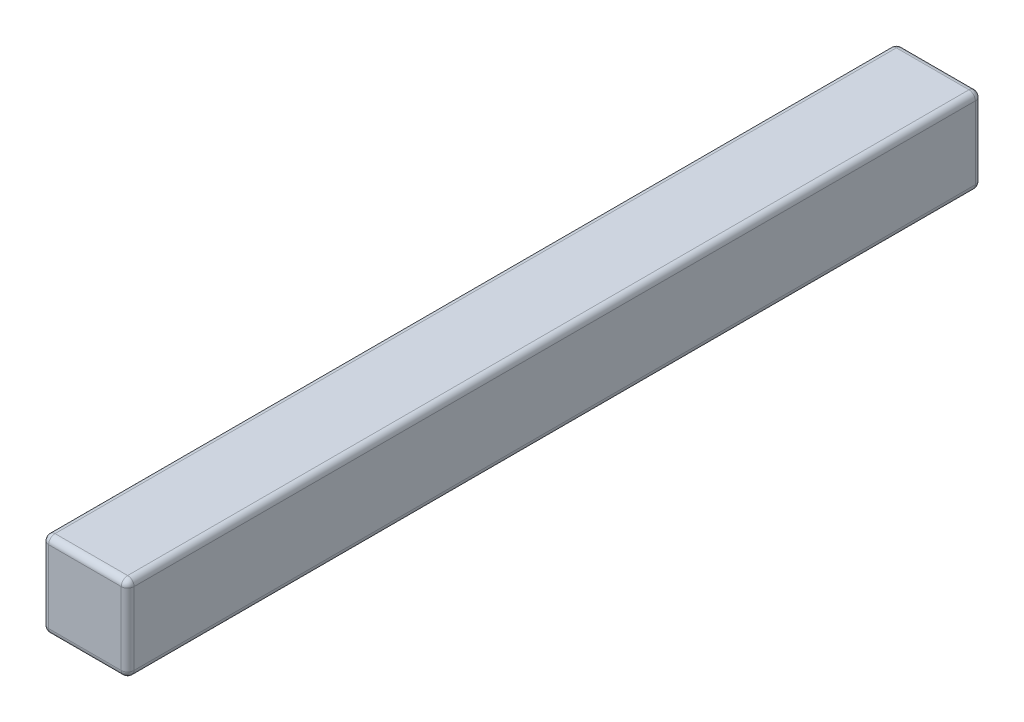
SolidWorks part; units mm, degrees
ref_plane "Front Plane" through (0, 0, 0) normal (0, 0, 1) x (1, 0, 0)
ref_plane "Top Plane" through (0, 0, 0) normal (0, 1, 0) x (1, 0, 0)
ref_plane "Right Plane" through (0, 0, 0) normal (1, 0, 0) x (0, 0, -1)
sketch "Sketch1" plane through (0, 0, 0) normal (0, 0, 1) x (1, 0, 0)
  line L3 (1, -1) -> (-1, -1)
  line L4 (1, -1) -> (1, 1)
  line L5 (1, 1) -> (-1, 1)
  line L6 (-1, -1) -> (-1, 1)
  line L7 (1, -1) -> (-1, 1) construction
  line L8 (1, 1) -> (-1, -1) construction
  point P0 (0, 0)
  dimension "Width" = 2
  dimension "Height" = 2
sketch "Sketch2" plane through (0, 0, 0) normal (1, 0, 0) x (0, 0, -1)
  line L2 (10, -1) -> (-10, -1)
  line L3 (10, -1) -> (10, 1)
  line L4 (10, 1) -> (-10, 1)
  line L5 (-10, -1) -> (-10, 1)
  line L6 (10, -1) -> (-10, 1) construction
  line L7 (10, 1) -> (-10, -1) construction
  point P0 (0, 0)
  point P4 (0, 0)
  point P15 (-7.8, 1)
  point P17 (7.8, 1)
  dimension "Length" = 20
  dimension "D1" = 2.2
  dimension "D2" = 2.2
sketch "Sketch3" plane through (0, 0, 0) normal (0, 0, 1) x (1, 0, 0)
  line L0 (1, -1) -> (1, 1) construction
  line L5 (1, -1) -> (-1, -1) construction
  line L6 (-1, -1) -> (-1, 1) construction
  line L7 (1, 1) -> (-1, 1) construction
  line L8 (1, -1) -> (1, 1)
  line L9 (1, -1) -> (-1, -1)
  line L10 (-1, -1) -> (-1, 1)
  line L11 (1, 1) -> (-1, 1)
extrude "Boss-Extrude1" add sketch "Sketch3" along normal up to vertex (10 mm away) and the other way up to vertex (10 mm away) up to point (0, 1, 10) other way up to point (0, 1, -10)
fillet "Fillet2" radius 0.15 12 edges at (-1, 0, -10) (0, -1, -10) (-1, 1, 0) (0, 1, -10) (1, 1, 0) (1, 0, -10) (1, -1, 0) (-1, 0, 10) (0, 1, 10) (1, 0, 10) (0, -1, 10) (-1, -1, 0)
ref_plane "Contact Plane 1" through (0, 0, 10) normal (0, 0, 1) x (1, 0, 0)
ref_plane "Contact Plane 2" through (0, 0, -10) normal (0, 0, 1) x (1, 0, 0)
ref_axis "Center Axis 1" through (0, 0, -27.5) along (0, 0, 1)
equation "\"D1@Sketch2\"=\"Width@Sketch1\"*1.1"
equation "\"D2@Sketch2\"=\"D1@Sketch2\""
